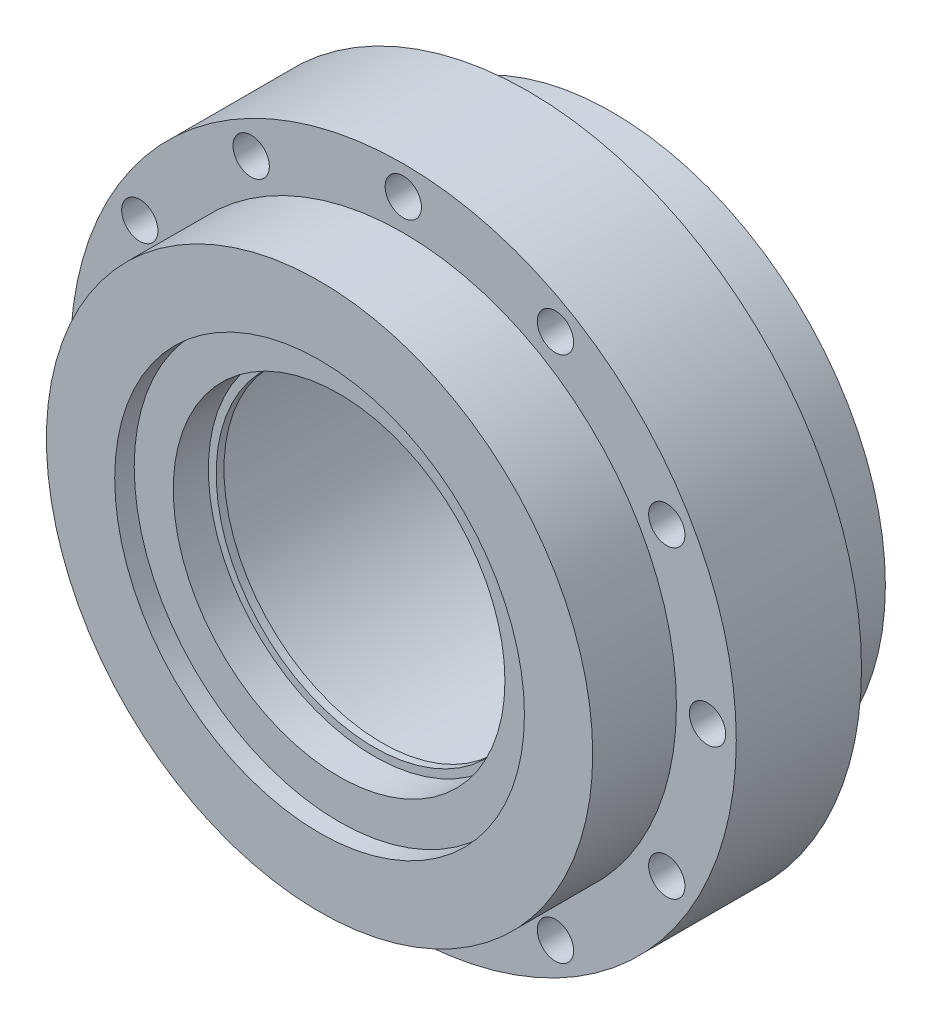
SolidWorks part; units mm, degrees
ref_plane "Front Plane" through (0, 0, 0) normal (0, 0, 1) x (1, 0, 0)
ref_plane "Top Plane" through (0, 0, 0) normal (0, 1, 0) x (1, 0, 0)
ref_plane "Right Plane" through (0, 0, 0) normal (1, 0, 0) x (0, 0, -1)
sketch "Sketch1" plane through (0, 0, 0) normal (1, 0, 0) x (0, 0, -1)
  line L0 (-84.7958, 52.5) -> (-79.7958, 52.5)
  line L1 (-73.3513, 52.5) -> (-74.0979, 52.5) construction
  line L2 (-68.7958, 40.5) -> (-70.7958, 40.5)
  line L3 (-50.0958, 55) -> (-67.2958, 55) construction
  line L4 (-84.7958, 52.5) -> (-84.7958, 70)
  line L5 (-84.7958, 70) -> (-9.7958, 70)
  line L7 (-79.7958, 52.5) -> (-79.7958, 42.5)
  line L10 (-68.7958, 53.5) -> (-68.7958, -53.5) construction
  line L11 (-68.7958, 40.5) -> (-68.7958, 55)
  line L12 (-68.7958, 55) -> (-9.7958, 55)
  line L13 (-70.7958, 40.5) -> (-70.7958, 42.5)
  line L14 (-9.7958, 70) -> (-9.7958, 55)
  line L16 (174.1864, 0) -> (-154.8488, 0) construction
  line L17 (-82.7958, 51.3889) -> (-82.7958, -51.3889) construction
  line L18 (-163.8227, 0) -> (139.4858, 0) construction
  line L19 (-70.7958, 42.5) -> (-79.7958, 42.5)
  point P14 (0, 0)
  point P15 (-72.7958, 42.5)
  dimension "D1" = 42.5
  dimension "D2" = 70
  dimension "D3" = 75
  dimension "D4" = 2
  dimension "D5" = 9
  dimension "D6" = 2
  dimension "D7" = 5
  dimension "D8" = 2
revolve "Revolve1" add sketch "Sketch1" angle 360 about L18
sketch "Sketch2" plane through (0, 0, 9.7958) normal (0, 0, -1) x (-1, 0, 0)
  line L0 (0, 62.5) -> (0, -62.5) construction
  circle A0 centre (0, 0) radius 62.5 construction
  circle A1 centre (0, 62.5) radius 4
  circle A2 centre (0, -62.5) radius 4
  dimension "D1" = 125
  dimension "D2" = 8
extrude "Cut-Extrude1" cut sketch "Sketch2" against normal blind 10
sketch "Sketch5" plane through (0, 0, 0) normal (0, 0, 1) x (1, 0, 0)
  line L0 (0, 70) -> (0, -70) construction
  line L3 (-31.25, 54.1266) -> (0, 0) construction
  line L8 (0, 62.5) -> (0, 0) construction
  line L9 (31.25, 54.1266) -> (0, 0) construction
  line L10 (54.1266, 31.25) -> (0, 0) construction
  line L11 (62.5, 0) -> (0, 0) construction
  line L12 (54.1266, -31.25) -> (0, 0) construction
  line L13 (31.25, -54.1266) -> (0, 0) construction
  line L14 (0, -62.5) -> (0, 0) construction
  line L15 (-31.25, -54.1266) -> (0, 0) construction
  line L16 (-54.1266, -31.25) -> (0, 0) construction
  line L17 (-62.5, 0) -> (0, 0) construction
  line L18 (-54.1266, 31.25) -> (0, 0) construction
  circle A0 centre (0, 0) radius 62.5 construction
  point P12 (-31.25, 54.1266)
  point P14 (-62.5, 0)
  point P15 (31.25, 54.1266)
  point P17 (62.5, 0)
  point P27 (54.1266, -31.25)
  point P28 (31.25, -54.1266)
  point P30 (-31.25, -54.1266)
  point P31 (-54.1266, -31.25)
  point P33 (-54.1266, 31.25)
  dimension "D1" = 125
  dimension "D3" = 12
  dimension "D2" = 30
hole_wizard "M8x1.25 Tapped Hole2" positions "Sketch5" profile "Sketch6" tap size "M8x1.25" standard "ANSI Metric"
sketch "Sketch6" plane through (-54.1266, 31.25, 0) normal (1, 0, 0) x (0, 1, 0)
  line L0 (0, 0) -> (0, 21.7929)
  line L1 (0, 21.7929) -> (3.4, 19.75)
  line L2 (3.4, 19.75) -> (3.4, 0)
  line L5 (3.4, 0) -> (0, 0)
  line L10 (0, 21.7929) -> (-3.4, 19.75) construction
  line L11 (0, -6.35) -> (0, 107.95) construction
  dimension "Tap Drill Dia." = 6.8
  dimension "Tap Drill Depth" = 19.75
  dimension "Drill Angle" = 118
cosmetic thread "Hole Thread8" parameters "D1"=16, "D2"=8
cosmetic thread "Hole Thread9" parameters "D1"=16, "D2"=8
cosmetic thread "Hole Thread10" parameters "D1"=16, "D2"=8
cosmetic thread "Hole Thread11" parameters "D1"=16, "D2"=8
cosmetic thread "Hole Thread12" parameters "D1"=16, "D2"=8
cosmetic thread "Hole Thread13" parameters "D1"=16, "D2"=8
cosmetic thread "Hole Thread14" parameters "D1"=16, "D2"=8
cosmetic thread "Hole Thread15" parameters "D1"=16, "D2"=8
cosmetic thread "Hole Thread16" parameters "D1"=16, "D2"=8
sketch "Sketch7" plane through (0, 0, 0) normal (1, 0, 0) x (0, 0, -1)
  line L0 (-31.2502, 70) -> (-63.3413, 70)
  line L1 (-84.7958, 70) -> (-9.7958, 70) construction
  line L2 (-63.3413, 70) -> (-63.3413, 85.3347)
  line L3 (-63.3413, 85.3347) -> (-31.2502, 85.3347)
  line L4 (-31.2502, 85.3347) -> (-31.2502, 70)
  point P5 (-47.2958, 70)
revolve "Revolve2" add sketch "Sketch7" angle 360 about L18
sketch "Sketch8" plane through (0, 0, 31.2502) normal (0, 0, -1) x (-1, 0, 0)
  circle A0 centre (0, 77.9691) radius 4.6522
  circle A1 centre (38.9846, 67.5233) radius 4.6522
  circle A2 centre (67.5233, 38.9846) radius 4.6522
  circle A3 centre (77.9691, 0) radius 4.6522
  circle A4 centre (67.5233, -38.9846) radius 4.6522
  circle A5 centre (38.9846, -67.5233) radius 4.6522
  circle A6 centre (0, -77.9691) radius 4.6522
  circle A7 centre (-38.9846, -67.5233) radius 4.6522
  circle A8 centre (-67.5233, -38.9846) radius 4.6522
  circle A9 centre (-77.9691, 0) radius 4.6522
  circle A10 centre (-67.5233, 38.9846) radius 4.6522
  circle A11 centre (-38.9846, 67.5233) radius 4.6522
  circle A12 centre (0, 0) radius 85.3347 construction
  point P29 (0, 0)
  dimension "D1" = 12
extrude "Cut-Extrude2" cut sketch "Sketch8" against normal through all
